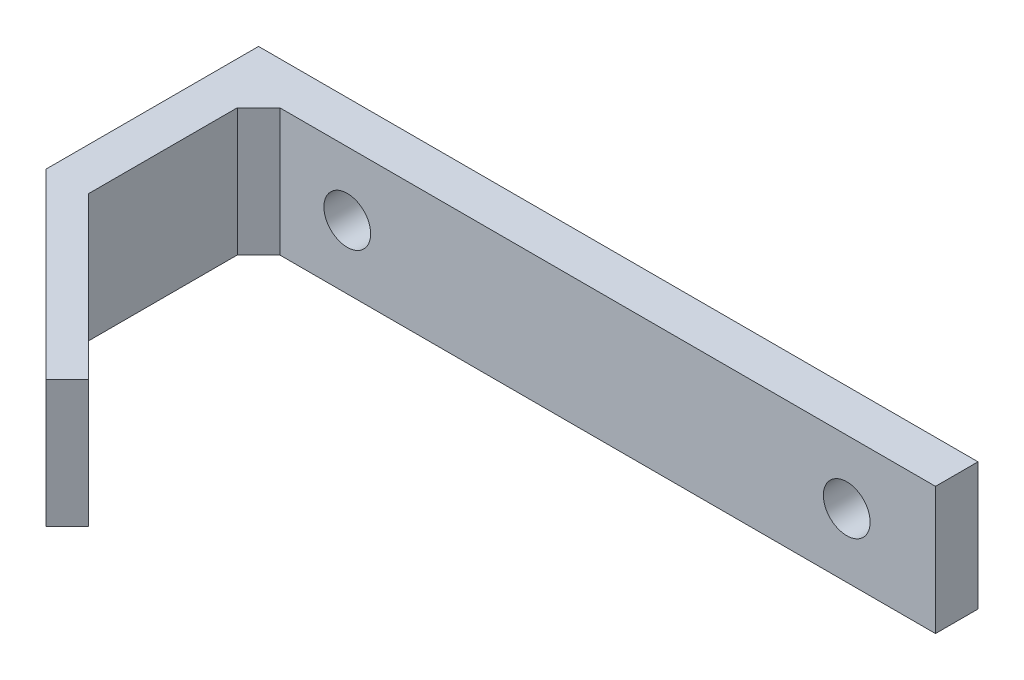
SolidWorks part; units mm, degrees
ref_plane "Front Plane" through (0, 0, 0) normal (0, 0, 1) x (1, 0, 0)
ref_plane "Top Plane" through (0, 0, 0) normal (0, 1, 0) x (1, 0, 0)
ref_plane "Right Plane" through (0, 0, 0) normal (1, 0, 0) x (0, 0, -1)
sketch "Sketch1" plane through (0, 0, 0) normal (0, 0, 1) x (1, 0, 0)
  line L0 (-11.75, 0) -> (11.75, 0)
  line L1 (15.925, -3) -> (-15.925, -3)
  line L2 (15.925, -3) -> (15.925, 3)
  line L3 (15.925, 3) -> (-15.925, 3)
  line L4 (-15.925, -3) -> (-15.925, 3)
  line L5 (15.925, -3) -> (-15.925, 3) construction
  line L6 (15.925, 3) -> (-15.925, -3) construction
  circle A0 centre (-11.75, 0) radius 1.1
  circle A1 centre (11.75, 0) radius 1.1
  point P0 (0, 0)
  point P9 (0, 0)
  dimension "D4" = 2.2
  dimension "D5" = 2.2
  dimension "D1" = 31.85
  dimension "D2" = 6
  dimension "D3" = 23.5
extrude "Boss-Extrude1" add sketch "Sketch1" along normal blind 2 contours L4 L1 L2 L3 A1 A0 region at (0, -2.6759, 0)
sketch "Sketch4" plane through (-15.925, 0, 0) normal (-1, 0, 0) x (0, 0, 1)
  line L0 (2, -3) -> (0, -3) construction
  line L1 (0, 3) -> (10, 3)
  line L2 (0, 3) -> (0, -3)
  line L3 (0, -3) -> (10, -3)
  line L4 (10, 3) -> (10, -3)
  dimension "D1" = 10
extrude "Boss-Extrude3" add sketch "Sketch4" along normal blind 2
sketch "Sketch5" plane through (0, -3, 0) normal (0, -1, 0) x (1, 0, 0)
  line L0 (-17.925, 10) -> (-9.3619, 18.5631)
  line L1 (-9.3619, 18.5631) -> (-8.3619, 17.5631)
  line L2 (-8.3619, 17.5631) -> (-15.925, 10)
  line L3 (-15.925, 2) -> (-15.925, 10) construction
  line L4 (-15.925, 10) -> (-17.925, 10)
  dimension "D1" = 135
extrude "Boss-Extrude4" add sketch "Sketch5" against normal up to surface (6 mm away) up to face at (-5.975, 3, 4)
sketch "Sketch6" plane through (-12.9625, 0, 12.9625) normal (0.7071, 0, -0.7071) x (-0.7071, 0, -0.7071)
  line L0 (-6.5063, 3) -> (-6.5063, -3) construction
  line L1 (-6.5063, 3) -> (4.1896, 3) construction
  circle A0 centre (-1.5063, 0) radius 1.6
  dimension "D1" = 3.2
  dimension "D2" = 5
  dimension "D3" = 3
extrude "Cut-Extrude1" cut sketch "Sketch6" against normal blind 2
chamfer "Chamfer1" distance 1 angle 45 1 edges at (-15.925, 0, 2)
